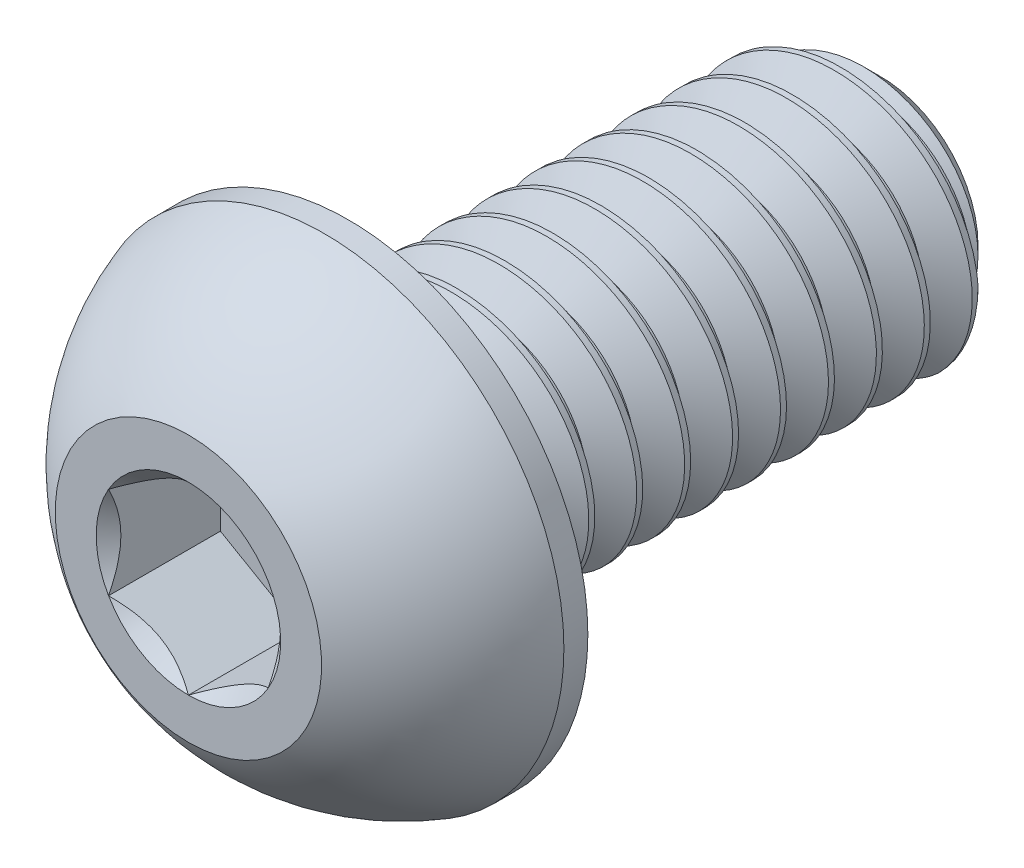
SolidWorks part; units mm, degrees
ref_plane "Front" through (0, 0, 0) normal (0, 0, 1) x (1, 0, 0)
ref_plane "Top" through (0, 0, 0) normal (0, 1, 0) x (1, 0, 0)
ref_plane "Right" through (0, 0, 0) normal (1, 0, 0) x (0, 0, -1)
sketch "Sketch1" plane through (0, 0, 0) normal (1, 0, 0) x (0, 0, -1)
  line L2 (1.5, 1.25) -> (6.5, 1.25)
  line L3 (6.5, 1.25) -> (6.5, 0)
  line L4 (6.5, 0) -> (1.5, 0)
  line L6 (1.275, 2.25) -> (1.5, 2.25) construction
  line L7 (6.5, 1.25) -> (6.5, -1.25) construction
  line L8 (0, 0) -> (1.5, 0) construction
  line L9 (1.5, 2.25) -> (1.5, -2.25) construction
  line L11 (1.5, 1.25) -> (1.5, 0)
  line L13 (0, 0.75) -> (0, -0.75) construction
  line L14 (0, 0.75) -> (0, 1.25) construction
  line L15 (6.4719, 1.2987) -> (6.6969, 0.909) construction
  line L16 (6.6969, 0.909) -> (6.9219, 1.2987) construction
  line L17 (6.9219, 1.2987) -> (6.4719, 1.2987) construction
  line L18 (6.5, 1.25) -> (6.8938, 1.25) construction
  line L19 (6.6969, 1.2987) -> (6.6969, 1.25) construction
  line L20 (6.6969, 1.25) -> (6.6969, 0.9577) construction
  line L21 (6.6969, 0.9577) -> (6.6969, 0.909) construction
  line L22 (6.6688, 0.9577) -> (6.725, 0.9577)
  line L23 (6.4859, 1.2744) -> (6.9078, 1.2744)
  line L24 (6.725, 0.9577) -> (6.9078, 1.2744)
  line L25 (6.6688, 0.9577) -> (6.4859, 1.2744)
  line L26 (6.1625, 1.25) -> (6.5, 0.9125)
  arc A3 (0, 1.25) -> (1.275, 2.25) centre (2.01, 0) cw construction
  point P29 (6.6969, 1.2744)
  point P30 (5.375, -1.25)
  dimension "D1" = 0.225
  dimension "Pitch" = 0.45
  dimension "D3" = 0.0563
  dimension "D2" = 0.3375
  dimension "D4" = 45
  dimension "D5" = 1.125
sketch "Sketch10" plane through (0, 0, 0) normal (1, 0, 0) x (0, 0, -1)
  line L0 (6.1625, 1.25) -> (6.5, 0.9125) construction
  line L1 (6.1625, 1.25) -> (6.5, 0.9125)
  line L4 (6.5, 1.25) -> (1.5, 1.25)
  line L5 (6.5, 0) -> (6.5, 1.25)
  line L6 (1.5, 0) -> (6.5, 0)
  line L7 (1.5, 1.25) -> (1.5, 0)
  line L8 (6.1625, 1.25) -> (1.5, 1.25)
  line L9 (6.5, 0) -> (6.5, 0.9125)
  line L10 (1.5, 0) -> (6.5, 0)
  line L11 (1.5, 1.25) -> (1.5, 0)
  dimension "D1" = 0
revolve "Revolve3" add sketch "Sketch10" angle 360 about L8
sketch "Sketch7" plane through (0, 0, 0) normal (1, 0, 0) x (0, 0, -1)
  line L6 (1.275, 2.25) -> (1.5, 2.25) construction
  line L8 (0, 0) -> (1.5, 0) construction
  line L11 (1.5, 2.25) -> (1.5, -2.25) construction
  line L12 (1.275, 2.25) -> (1.5, 2.25)
  line L13 (0, 0) -> (1.5, 0)
  line L14 (0, 0.75) -> (0, -0.75) construction
  line L15 (1.5, 2.25) -> (1.5, 0)
  line L16 (0, 1.25) -> (0, 0)
  arc A2 (1.275, 2.25) -> (0, 1.25) centre (2.01, 0) ccw construction
  arc A3 (1.275, 2.25) -> (0, 1.25) centre (2.01, 0) ccw
revolve "Revolve2" add sketch "Sketch7" angle 360 mid plane about L13
sketch "Sketch5" plane through (0, 0, 0) normal (0, 0, 1) x (1, 0, 0)
  line L1 (0.75, -0.433) -> (0.75, 0.433)
  line L2 (0.75, 0.433) -> (0, 0.866)
  line L3 (0, 0.866) -> (-0.75, 0.433)
  line L4 (-0.75, 0.433) -> (-0.75, -0.433)
  line L5 (-0.75, -0.433) -> (0, -0.866)
  line L6 (0, -0.866) -> (0.75, -0.433)
  circle A0 centre (0, 0) radius 0.75 construction
extrude "Cut-Extrude2" cut sketch "Sketch5" against normal blind 1.05
sketch "Sketch6" plane through (0, 0, 0) normal (0, 0, 1) x (1, 0, 0)
  circle A0 centre (0, 0) radius 0.866
extrude "Cut-Extrude3" cut sketch "Sketch6" against normal blind 1.05 draft 45
sketch "Sketch9" plane through (0, 0, -1.5) normal (0, 0, -1) x (-1, 0, 0)
  circle A0 centre (0, 0) radius 1.25 construction
  circle A4 centre (0, 0) radius 1.25
split "Split1" bodies to split 113 resulting bodies 123 124 split by face at (2.25, 0, -1.5)
sketch "Sketch11" plane through (0, 0, -6.5) normal (0, 0, -1) x (-1, 0, 0)
  circle A0 centre (0, 0) radius 1.25 construction
  circle A1 centre (0, 0) radius 1.25
curve "Helix/Spiral1" pitch 0.45 height 6.5 radius 1.25 centre (0, 0, -6.5) axis (0, 0, 1) start towards (0, 1, 0)
sketch "Sketch12" plane through (0, 0, 0) normal (1, 0, 0) x (0, 0, -1)
  line L0 (6.6688, 0.9577) -> (6.725, 0.9577) construction
  line L1 (6.725, 0.9577) -> (6.9078, 1.2744) construction
  line L2 (6.4859, 1.2744) -> (6.9078, 1.2744) construction
  line L3 (6.6688, 0.9577) -> (6.4859, 1.2744) construction
  line L4 (6.6688, 0.9577) -> (6.725, 0.9577)
  line L5 (6.725, 0.9577) -> (6.9078, 1.2744)
  line L6 (6.4859, 1.2744) -> (6.9078, 1.2744)
  line L7 (6.6688, 0.9577) -> (6.4859, 1.2744)
sweep "Cut-Sweep2" cut profiles "Sketch12" path "Helix/Spiral1" align with end faces yes
extrude "Boss-Extrude1" add sketch "Sketch9" along normal blind 10 draft 45
equation "\"D1@Cut-Extrude2\" = \"Head Ht@Sketch1\" * .7"
equation "\"D1@Sketch1\" = \"Head Ht@Sketch1\" * .15"
equation "\"D1@Cut-Extrude3\" = \"D1@Cut-Extrude2\""
equation "\"D3@Sketch1\" = \"Pitch@Sketch1\" / 8"
equation "\"D2@Sketch1\"=\"Pitch@Sketch1\"*0.75"
equation "\"D3@Helix/Spiral1\" = \"Lg@Sketch1\" + \"Head Ht@Sketch1\""
equation "\"D4@Helix/Spiral1\"=\"pitch@sketch1\""
equation "\"D5@Sketch1\"=\"Pitch@Sketch1\"*2.5"
